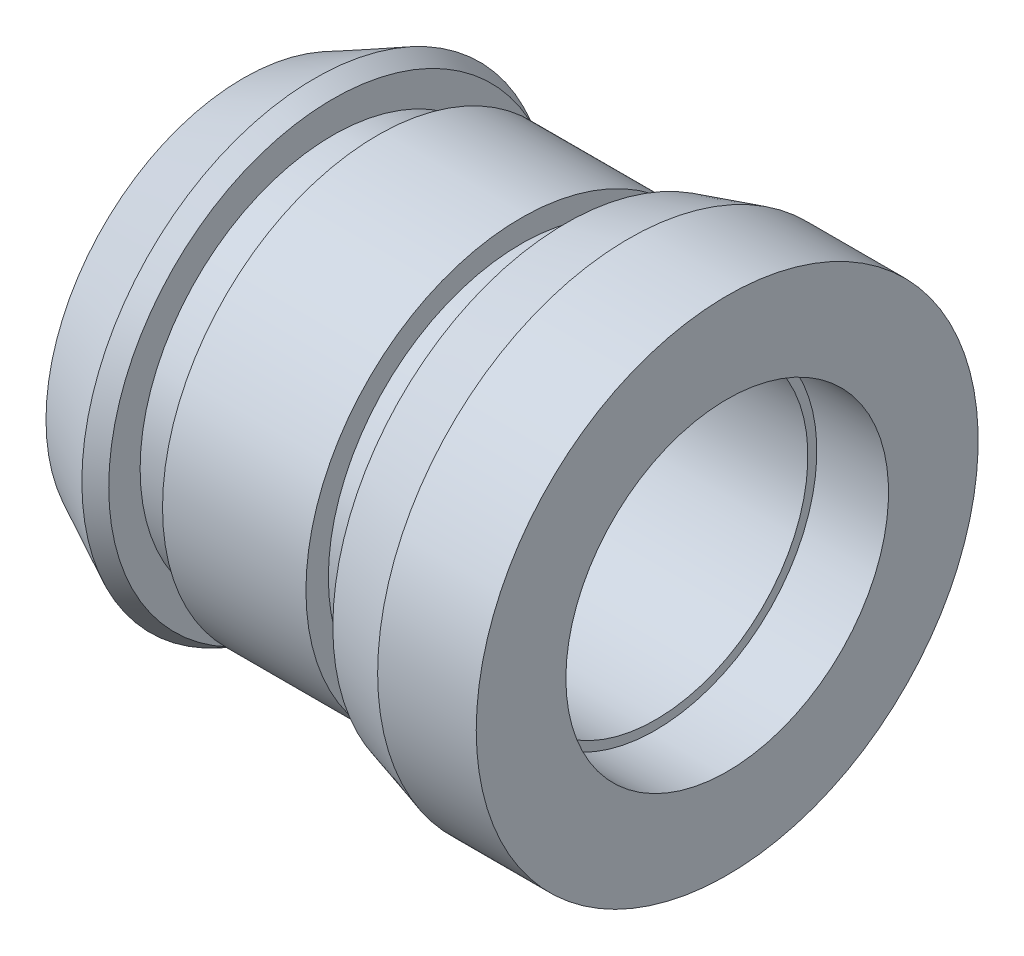
SolidWorks part; units mm, degrees
ref_plane "Front Plane" through (0, 0, 0) normal (0, 0, 1) x (1, 0, 0)
ref_plane "Top Plane" through (0, 0, 0) normal (0, 1, 0) x (1, 0, 0)
ref_plane "Right Plane" through (0, 0, 0) normal (1, 0, 0) x (0, 0, -1)
sketch "Sketch1" plane through (0, 0, 0) normal (0, 1, 0) x (1, 0, 0)
  line L0 (-96.8188, 0) -> (98.7644, 0) construction
  line L1 (-49.2125, 28.575) -> (-49.2125, 34.925)
  line L2 (-49.2125, 34.925) -> (-36.5125, 41.275)
  line L3 (-36.5125, 41.275) -> (-33.3375, 39.6875)
  line L4 (-33.3375, 39.6875) -> (-33.3375, 34.1312)
  line L5 (-33.3375, 34.1312) -> (-25.4, 34.1313)
  line L6 (-25.4, 34.1313) -> (-25.4, 38.1)
  line L7 (-25.4, 38.1) -> (0, 38.1)
  line L8 (0, 38.1) -> (0, 34.1313)
  line L9 (0, 34.1313) -> (7.9375, 34.1313)
  line L10 (7.9375, 34.1313) -> (7.9375, 41.275)
  line L11 (7.9375, 41.275) -> (19.05, 44.45)
  line L12 (19.05, 44.45) -> (36.5125, 44.45)
  line L13 (36.5125, 44.45) -> (36.5125, 28.575)
  line L16 (23.8125, 26.9875) -> (23.8125, 28.575)
  line L17 (23.8125, 28.575) -> (36.5125, 28.575)
  line L21 (23.8125, 26.9875) -> (-23.8125, 26.9875)
  line L22 (-23.8125, 26.9875) -> (-23.8125, 28.575)
  line L23 (-23.8125, 28.575) -> (-49.2125, 28.575)
  dimension "D1" = 12.7
  dimension "D2" = 3.175
  dimension "D3" = 7.9375
  dimension "D4" = 25.4
  dimension "D5" = 7.9375
  dimension "D6" = 11.1125
  dimension "D7" = 17.4625
  dimension "D9" = 34.925
  dimension "D10" = 41.275
  dimension "D11" = 39.6875
  dimension "D12" = 34.1313
  dimension "D13" = 38.1
  dimension "D14" = 41.275
  dimension "D15" = 44.45
  dimension "D16" = 28.575
  dimension "D17" = 12.7
  dimension "D8" = 25.4
  dimension "D18" = 26.9875
revolve "Revolve1" add sketch "Sketch1" angle 360 about L0
equation "\"D9@Sketch1\"=(2+3/4)/2in"
equation "\"D10@Sketch1\"=(3+1/4)/2"
equation "\"D11@Sketch1\"=(3+1/8)/2"
equation "\"D12@Sketch1\"=(2+11/16)/2"
equation "\"D14@Sketch1\"=(3+1/4)/2"
equation "\"D15@Sketch1\"=(3+1/2)/2"
equation "\"D16@Sketch1\"=(2+1/4)/2"
